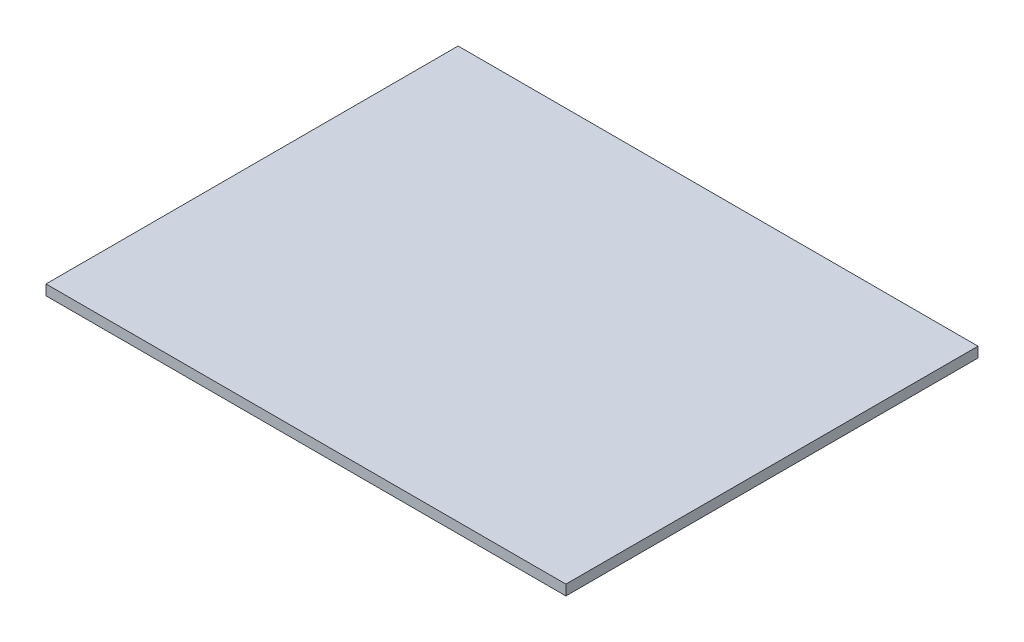
SolidWorks part; units mm, degrees
material "Oak"
ref_plane "Front" through (0, 0, 0) normal (0, 0, 1) x (1, 0, 0)
ref_plane "Top" through (0, 0, 0) normal (0, 1, 0) x (1, 0, 0)
ref_plane "Right" through (0, 0, 0) normal (1, 0, 0) x (0, 0, -1)
sketch "Sketch1" plane through (0, 0, 0) normal (0, 0, 1) x (1, 0, 0)
  line L0 (-240.475, 9.525) -> (240.475, 9.525)
  line L1 (-250, 0) -> (250, 0)
  line L2 (-250, 0) -> (-250, 500)
  line L3 (-250, 500) -> (250, 500)
  line L4 (250, 0) -> (250, 500)
  line L5 (240.475, 9.525) -> (240.475, 490.475)
  line L6 (-240.475, 490.475) -> (240.475, 490.475)
  line L7 (-240.475, 9.525) -> (-240.475, 490.475)
  line L8 (-140.1808, 490.475) -> (-140.1808, 373.0167) construction
  line L9 (-240.475, 373.0167) -> (240.475, 373.0167)
  line L10 (-240.475, 373.0167) -> (-240.475, 363.4917)
  line L11 (-240.475, 363.4917) -> (240.475, 363.4917)
  line L12 (240.475, 373.0167) -> (240.475, 363.4917)
  line L13 (-240.475, 246.0333) -> (240.475, 246.0333)
  line L14 (-240.475, 246.0333) -> (-240.475, 236.5083)
  line L15 (-240.475, 236.5083) -> (240.475, 236.5083)
  line L16 (240.475, 246.0333) -> (240.475, 236.5083)
  line L17 (-240.475, 119.05) -> (240.475, 119.05)
  line L18 (-240.475, 119.05) -> (-240.475, 109.525)
  line L19 (-240.475, 109.525) -> (240.475, 109.525)
  line L20 (240.475, 119.05) -> (240.475, 109.525)
  line L21 (-140.1808, 363.4917) -> (-140.1808, 246.0333) construction
  line L22 (-140.1808, 236.5083) -> (-140.1808, 119.05) construction
  line L23 (-240.475, 431.7458) -> (-86.5083, 431.7458) construction
  line L24 (-86.5083, 490.475) -> (-76.9833, 490.475)
  line L25 (-86.5083, 490.475) -> (-86.5083, 373.0167)
  line L26 (-86.5083, 373.0167) -> (-76.9833, 373.0167)
  line L27 (-76.9833, 490.475) -> (-76.9833, 373.0167)
  line L28 (76.9833, 490.475) -> (86.5083, 490.475)
  line L29 (76.9833, 490.475) -> (76.9833, 373.0167)
  line L30 (76.9833, 373.0167) -> (86.5083, 373.0167)
  line L31 (86.5083, 490.475) -> (86.5083, 373.0167)
  line L32 (-76.9833, 431.7458) -> (76.9833, 431.7458) construction
  line L33 (86.5083, 431.7458) -> (240.475, 431.7458) construction
  dimension "D1" = 500
  dimension "D2" = 9.525
  dimension "D3" = 9.525
  dimension "D4" = 100
  dimension "D5" = 9.525
  dimension "D6" = 117.4583
  dimension "D7" = 153.9667
extrude "Boss-Extrude1" add sketch "Sketch1" along normal blind 381.25 contours L17 L20 L19 L18
